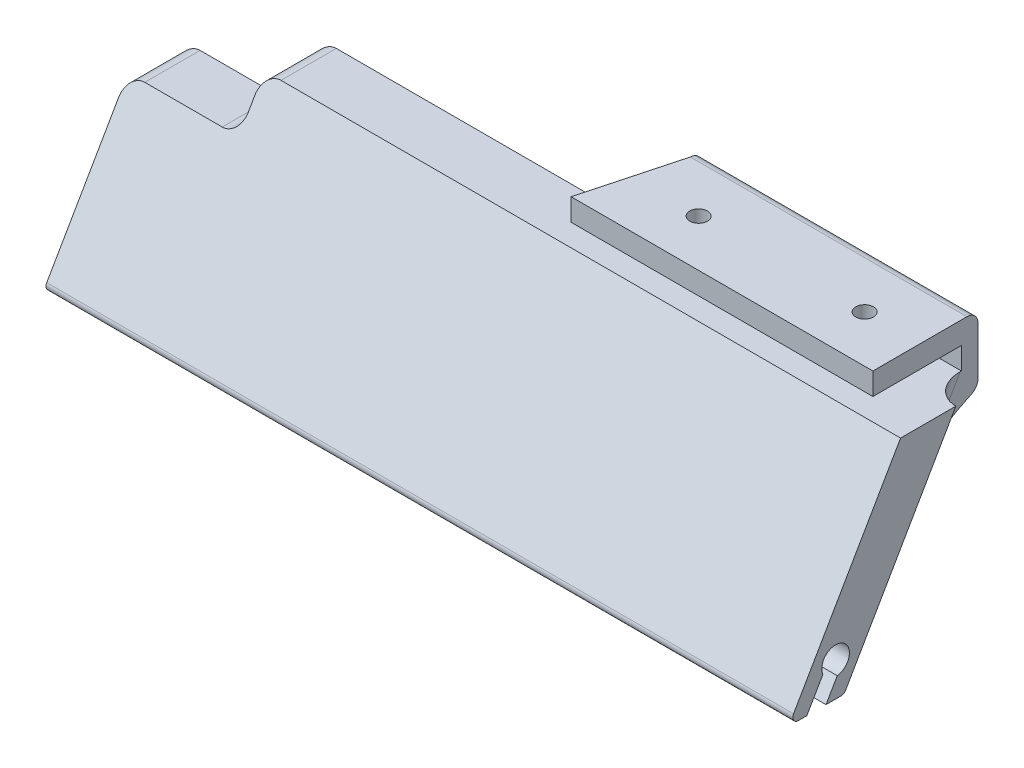
SolidWorks part; units mm, degrees
ref_plane "Front Plane" through (0, 0, 0) normal (0, 0, 1) x (1, 0, 0)
ref_plane "Top Plane" through (0, 0, 0) normal (0, 1, 0) x (1, 0, 0)
ref_plane "Right Plane" through (0, 0, 0) normal (1, 0, 0) x (0, 0, -1)
sketch "Sketch2" plane through (0, 0, 0) normal (1, 0, 0) x (0, 0, -1)
  line L0 (0, 0) -> (20.2073, 35)
  line L1 (20.2073, 35) -> (30.2073, 35)
  line L2 (30.2073, 35) -> (10, 0)
  line L3 (10, 0) -> (0, 0)
  line L4 (0, 0) -> (0, 35) construction
  line L5 (25.2073, 35) -> (5, 0) construction
  line L6 (3.2679, 0) -> (7.1651, 6.75)
  line L7 (7.1651, 6.75) -> (9.7631, 5.25)
  line L8 (9.7631, 5.25) -> (6.7321, 0)
  line L34 (20.2073, 35) -> (39.2073, 35)
  line L35 (20.2073, 35) -> (20.2073, 31)
  line L36 (20.2073, 31) -> (39.2073, 31)
  line L37 (39.2073, 35) -> (39.2073, 31)
  line L38 (39.2073, 35) -> (36.2073, 35)
  line L39 (39.2073, 35) -> (39.2073, 39)
  line L40 (39.2073, 39) -> (36.2073, 39)
  line L41 (36.2073, 35) -> (36.2073, 39)
  line L42 (39.2073, 39) -> (20.2073, 39)
  line L43 (39.2073, 39) -> (39.2073, 43)
  line L44 (39.2073, 43) -> (20.2073, 43)
  line L45 (20.2073, 39) -> (20.2073, 43)
  circle A0 centre (8.4641, 6) radius 2.5
  point P14 (8.4641, 6)
  dimension "D5" = 5
  dimension "D1" = 30
  dimension "D2" = 10
  dimension "D3" = 35
  dimension "D4" = 3
  dimension "D6" = 6
  dimension "D7" = 4
  dimension "D8" = 4
  dimension "D9" = 3
  dimension "D10" = 6
extrude "Boss-Extrude2" add sketch "Sketch2" along normal blind 50 contours L45 L42 L40 L43 L44 | L41 L34 L39 L40 | L37 L34 L2 L36 | L35 L36 L2 L1 | A0 L8 L3 L2 L36 L35 L0 L6 region at (0, 17.0999, -14.8085) region at (0, 33.087, -24.655) region at (0, 32.9242, -34.108) region at (0, 37, -37.7073) region at (0, 41, -29.7073)
sketch "Sketch3" plane through (50, 0, 0) normal (1, 0, 0) x (0, 0, -1)
  line L0 (0, 0) -> (20.2073, 35)
  line L2 (20.2073, 35) -> (30.2073, 35)
  line L3 (30.2073, 35) -> (10, 0)
  line L4 (10, 0) -> (6.7321, 0)
  line L5 (6.7321, 0) -> (8.7631, 3.5179)
  line L6 (8.7631, 3.5179) -> (6.1651, 5.0179)
  line L7 (6.1651, 5.0179) -> (3.2679, 0)
  line L8 (3.2679, 0) -> (0, 0)
  line L9 (20.2073, 35) -> (36.2073, 35) construction
  line L10 (0, 0) -> (20.2073, 35) construction
  circle A0 centre (8.4641, 6) radius 2.5
  arc A1 (8.7631, 3.5179) -> (6.1651, 5.0179) centre (8.4641, 6) ccw construction
  line M14 (20.2073, 35) -> (0, 0)
  line M15 (0, 0) -> (3.2679, 0)
  line M16 (3.2679, 0) -> (6.1651, 5.0179)
  arc M17 (6.1651, 5.0179) -> (8.7631, 3.5179) centre (8.4641, 6) cw
  line M18 (8.7631, 3.5179) -> (6.7321, 0)
  line M19 (6.7321, 0) -> (10, 0)
  line M20 (10, 0) -> (27.8979, 31)
extrude "Boss-Extrude3" add sketch "Sketch3" along normal blind 5 and the other way blind 130 contours L2 M14 M15 M16 M17 M18 M19 M20 region at (50, 18.8865, -15.9088)
fillet "Fillet5" radius 50 1 edges at (25, 31, -27.8979)
fillet "Fillet6" radius 5 2 edges at (0, 22.5778, -23.0353) (50, 22.5778, -23.0353)
fillet "Fillet7" radius 2 2 edges at (25, 43, -39.2073) (25, 31, -39.2073)
fillet "Fillet8" radius 1 2 edges at (-12.5, 0, -10) (-12.5, 0, 0)
sketch "Sketch4" plane through (0, 0, -39.2073) normal (0, 0, -1) x (-1, 0, 0)
  line L1 (80, 35) -> (60, 35)
  line L2 (80, 35) -> (80, 27)
  line L3 (80, 27) -> (60, 27)
  line L4 (60, 35) -> (60, 27)
  dimension "D1" = 8
  dimension "D2" = 20
extrude "Cut-Extrude1" cut sketch "Sketch4" against normal through all
fillet "Fillet9" radius 3 3 edges at (-60, 27, -20.5885) (-60, 35, -25.2073) (-80, 27, -20.5885)
sketch "Sketch5" plane through (0, 43, 0) normal (0, 1, 0) x (1, 0, 0)
  line L0 (0, 37.2073) -> (-4.5551, 20.2073)
  line L1 (-4.5551, 20.2073) -> (0, 20.2073)
  line L2 (0, 20.2073) -> (0, 37.2073)
  line L3 (50, 20.2073) -> (0, 20.2073) construction
  dimension "D1" = 15
extrude "Boss-Extrude4" add sketch "Sketch5" against normal up to surface (4 mm away) up to face at (25, 39, -28.2073)
sketch "Sketch6" plane through (0, 43, 0) normal (0, 1, 0) x (1, 0, 0)
  line L0 (50, 28.7073) -> (-2.2776, 28.7073) construction
  line L1 (50, 37.2073) -> (50, 20.2073) construction
  line L2 (0, 37.2073) -> (-4.5551, 20.2073) construction
  circle A0 centre (10, 28.7073) radius 1.6
  circle A1 centre (40, 28.7073) radius 1.6
  dimension "D1" = 3.2
  dimension "D2" = 10
  dimension "D3" = 10
extrude "Cut-Extrude2" cut sketch "Sketch6" against normal through all
ref_plane "Plane1" through (0, 32, 0) normal (0, 1, 0) x (1, 0, 0)
sketch "Sketch7" plane through (0, 32, 0) normal (0, 1, 0) x (1, 0, 0)
  circle A0 centre (10, 28.7073) radius 3.5
  circle A1 centre (40, 28.7073) radius 3.5
  dimension "D1" = 7
extrude "Cut-Extrude3" cut sketch "Sketch7" against normal through all
